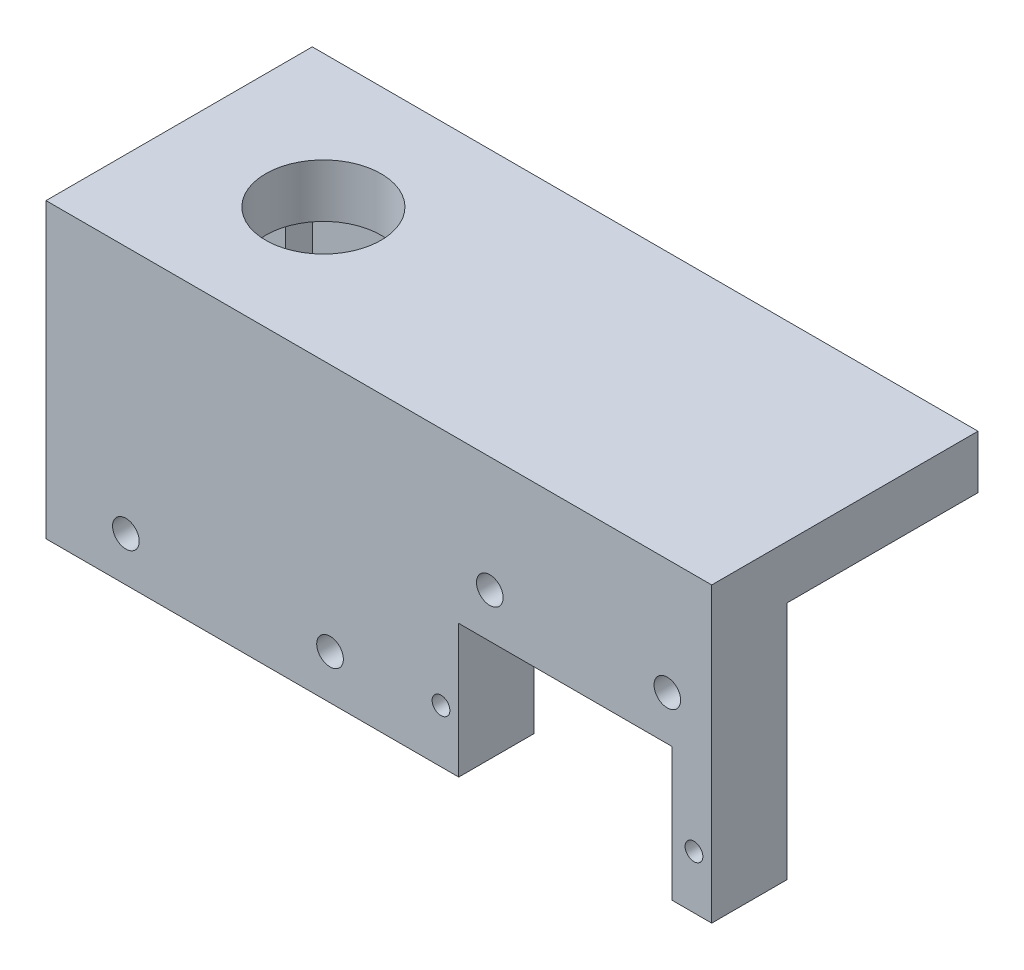
SolidWorks part; units mm, degrees
ref_plane "Front Plane" through (0, 0, 0) normal (0, 0, 1) x (1, 0, 0)
ref_plane "Top Plane" through (0, 0, 0) normal (0, 1, 0) x (1, 0, 0)
ref_plane "Right Plane" through (0, 0, 0) normal (1, 0, 0) x (0, 0, -1)
sketch "Sketch1" plane through (0, -4.342, 0) normal (0, -1, 0) x (1, 0, 0)
  line L0 (-40.9843, 28.2004) -> (-18.4843, 28.2004) construction
  line L1 (-11.5696, 28.2004) -> (-86.5696, 28.2004)
  line L2 (-11.5696, 28.2004) -> (-11.5696, -1.7996)
  line L3 (-11.5696, -1.7996) -> (-86.5696, -1.7996)
  line L4 (-86.5696, 28.2004) -> (-86.5696, -1.7996)
  dimension "D1" = 75
  dimension "D2" = 30
extrude "Boss-Extrude1" add sketch "Sketch1" along normal blind 6 contours L1 L4 L3 L2
sketch "Sketch2" plane through (0, -10.342, 0) normal (0, -1, 0) x (-1, 0, 0)
  line L1 (86.5696, 1.7996) -> (38.5696, 1.7996)
  line L2 (86.5696, 1.7996) -> (86.5696, -2.7004)
  line L3 (86.5696, -2.7004) -> (38.5696, -2.7004)
  line L4 (38.5696, 1.7996) -> (38.5696, -2.7004)
  line L5 (38.5696, 1.7996) -> (43.5696, 1.7996)
  line L6 (38.5696, 1.7996) -> (38.5696, -7.2004)
  line L7 (38.5696, -7.2004) -> (43.5696, -7.2004)
  line L8 (43.5696, 1.7996) -> (43.5696, -7.2004)
  line L9 (11.5696, -28.2004) -> (86.5696, -28.2004) construction
  line L10 (86.5696, 1.7996) -> (82.0696, 1.7996)
  line L11 (86.5696, 1.7996) -> (86.5696, -28.2004)
  line L12 (86.5696, -28.2004) -> (82.0696, -28.2004)
  line L13 (82.0696, 1.7996) -> (82.0696, -28.2004)
  line L14 (11.5696, -28.2004) -> (11.5696, 1.7996) construction
  line L15 (86.5696, -28.2004) -> (40.0696, -28.2004)
  line L16 (86.5696, -28.2004) -> (86.5696, -23.7004)
  line L17 (86.5696, -23.7004) -> (40.0696, -23.7004)
  line L18 (40.0696, -28.2004) -> (40.0696, -23.7004)
  line L19 (46.0696, -28.2004) -> (40.0696, -28.2004)
  line L20 (46.0696, -28.2004) -> (46.0696, -19.7004)
  line L21 (46.0696, -19.7004) -> (40.0696, -19.7004)
  line L22 (40.0696, -28.2004) -> (40.0696, -19.7004)
  line L24 (11.5696, -28.2004) -> (16.0696, -28.2004)
  line L25 (11.5696, -28.2004) -> (11.5696, -19.7004)
  line L26 (11.5696, -19.7004) -> (16.0696, -19.7004)
  line L27 (16.0696, -28.2004) -> (16.0696, -19.7004)
  dimension "D1" = 4.5
  dimension "D2" = 48
  dimension "D3" = 5
  dimension "D4" = 9
  dimension "D5" = 4.5
  dimension "D6" = 4.5
  dimension "D7" = 0
  dimension "D8" = 28.5
  dimension "D9" = 40.5
  dimension "D10" = 8.5
  dimension "D11" = 8.5
  dimension "D12" = 4.5
extrude "Boss-Extrude4" add sketch "Sketch2" along normal blind 27 contours L16 L15 L18 L17 | L2 L1 L4 L3 | L11 L10 L13 L12 | L6 L5 L8 L7 | L20 L19 L22 L21 | L25 L24 L27 L26
sketch "Sketch7" plane through (-38.5696, 0, 0) normal (1, 0, 0) x (0, 0, -1)
  line L1 (-7.2004, -37.342) -> (-2.7004, -37.342)
  line L2 (-7.2004, -37.342) -> (-7.2004, -22.342)
  line L3 (-7.2004, -22.342) -> (-2.7004, -22.342)
  line L4 (-2.7004, -37.342) -> (-2.7004, -22.342)
  dimension "D1" = 15
  dimension "D2" = 4.5
extrude "Cut-Extrude1" cut sketch "Sketch7" against normal blind 6
sketch "Sketch9" plane through (0, -4.342, 0) normal (0, 1, 0) x (1, 0, 0)
  line L1 (-86.5696, -28.2004) -> (-86.5696, 1.7996) construction
  line L2 (-11.5696, 1.7996) -> (-86.5696, 1.7996) construction
  circle A0 centre (-70.3196, -13.2004) radius 6.5
  dimension "D1" = 16.25
  dimension "D2" = 15
  dimension "D3" = 13
extrude "Cut-Extrude2" cut sketch "Sketch9" against normal blind 30
sketch "Sketch10" plane through (0, 0, 28.2004) normal (0, 0, 1) x (1, 0, 0)
  line L0 (-86.5696, -37.342) -> (-86.5696, -4.342) construction
  line L2 (-86.5696, -37.342) -> (-40.0696, -37.342) construction
  circle A0 centre (-77.5696, -32.342) radius 1.5
  dimension "D1" = 9
  dimension "D2" = 3
  dimension "D3" = 5
extrude "Cut-Extrude3" cut sketch "Sketch10" against normal blind 50
sketch "Sketch11" plane through (0, 0, 28.2004) normal (0, 0, 1) x (1, 0, 0)
  line L0 (-86.5696, -37.342) -> (-86.5696, -4.342) construction
  circle A0 centre (-54.5696, -32.342) radius 1.5
  circle A1 centre (-77.5696, -32.342) radius 1.5 construction
  dimension "D1" = 32
  dimension "D2" = 3
  dimension "D3" = 0
extrude "Cut-Extrude4" cut sketch "Sketch11" against normal blind 10
sketch "Sketch12" plane through (-86.5696, 0, 0) normal (-1, 0, 0) x (0, 0, 1)
  line L0 (-1.7996, -37.342) -> (28.2004, -37.342) construction
  line L1 (5.7004, -37.342) -> (20.7004, -37.342)
  line L2 (5.7004, -37.342) -> (5.7004, -11.342)
  line L3 (5.7004, -11.342) -> (20.7004, -11.342)
  line L4 (20.7004, -37.342) -> (20.7004, -11.342)
  line L5 (28.2004, -4.342) -> (-1.7996, -4.342) construction
  point P8 (13.2004, -4.342)
  dimension "D1" = 15
  dimension "D2" = 7.5
  dimension "D3" = 26
extrude "Cut-Extrude5" cut sketch "Sketch12" against normal blind 5
sketch "Sketch14" plane through (-40.0696, 0, 0) normal (1, 0, 0) x (0, 0, -1)
  line L1 (-19.7004, -22.342) -> (-28.2004, -22.342)
  line L2 (-19.7004, -22.342) -> (-19.7004, -10.342)
  line L3 (-19.7004, -10.342) -> (-28.2004, -10.342)
  line L4 (-28.2004, -22.342) -> (-28.2004, -10.342)
  dimension "D1" = 12
extrude "Boss-Extrude6" add sketch "Sketch14" along normal up to vertex (24 mm away) up to point (-16.0696, -10.342, 28.2004)
sketch "Sketch15" plane through (0, 0, 28.2004) normal (0, 0, 1) x (1, 0, 0)
  line L0 (-11.5696, -37.342) -> (-16.0696, -37.342) construction
  line L1 (-11.5696, -37.342) -> (-11.5696, -4.342) construction
  line L2 (-40.0696, -37.342) -> (-40.0696, -22.342) construction
  circle A0 centre (-13.5696, -31.342) radius 1
  circle A1 centre (-42.0696, -31.342) radius 1
  dimension "D1" = 2
  dimension "D2" = 6
  dimension "D3" = 2
  dimension "D4" = 0
  dimension "D5" = 2
  dimension "D6" = 2
extrude "Cut-Extrude6" cut sketch "Sketch15" against normal blind 11
sketch "Sketch16" plane through (0, 0, 19.7004) normal (0, 0, -1) x (-1, 0, 0)
  line L1 (11.5696, -37.342) -> (11.5696, -10.342) construction
  line L2 (16.0696, -22.342) -> (40.0696, -22.342) construction
  circle A0 centre (36.5696, -17.342) radius 1.5
  circle A1 centre (16.5696, -17.342) radius 1.5
  dimension "D1" = 3
  dimension "D2" = 3
  dimension "D3" = 5
  dimension "D4" = 5
  dimension "D5" = 5
  dimension "D6" = 20
extrude "Cut-Extrude7" cut sketch "Sketch16" against normal blind 11
